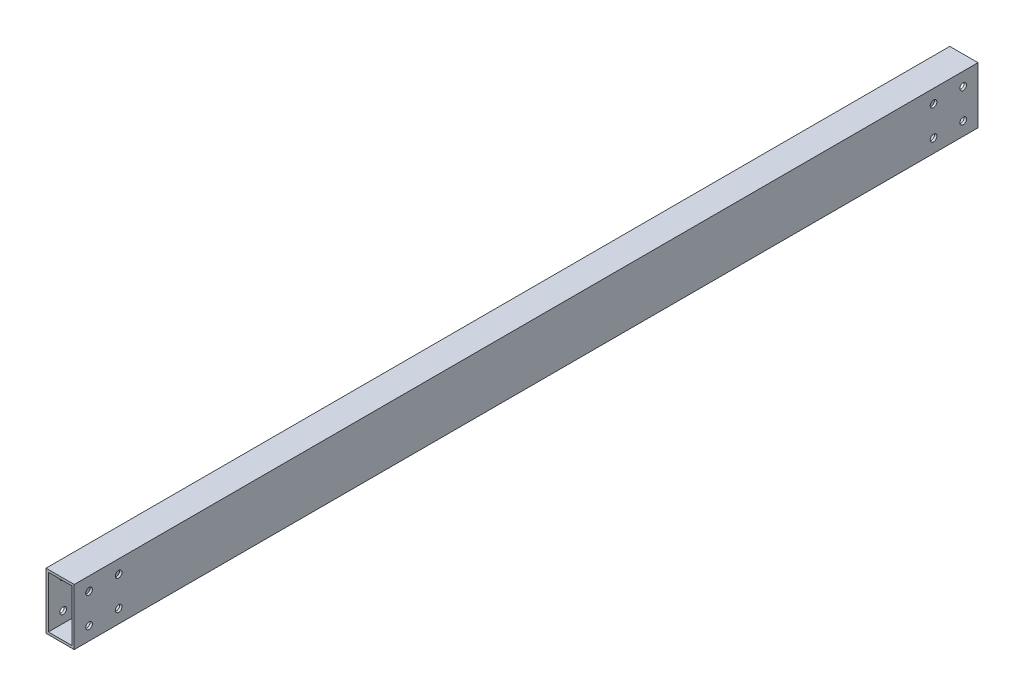
SolidWorks part; units mm, degrees
material "6061-T6 (SS)"
ref_plane "Front Plane" through (0, 0, 0) normal (0, 0, 1) x (1, 0, 0)
ref_plane "Top Plane" through (0, 0, 0) normal (0, 1, 0) x (1, 0, 0)
ref_plane "Right Plane" through (0, 0, 0) normal (1, 0, 0) x (0, 0, -1)
sketch "Sketch1" plane through (0, 0, 0) normal (0, 0, 1) x (1, 0, 0)
  line L1 (-19.05, 38.1) -> (19.05, 38.1)
  line L2 (-19.05, 38.1) -> (-19.05, -38.1)
  line L3 (-19.05, -38.1) -> (19.05, -38.1)
  line L4 (19.05, 38.1) -> (19.05, -38.1)
  line L5 (-19.05, 38.1) -> (19.05, -38.1) construction
  line L6 (-19.05, -38.1) -> (19.05, 38.1) construction
  point P0 (0, 0)
  dimension "D1" = 38.1
  dimension "D2" = 76.2
extrude "Extrude-Thin1" add sketch "Sketch1" along normal mid plane 1220 thin thin type one direction reverse wall 3.175
hole_wizard "M8 Clearance Hole2" positions "Sketch2" profile "Sketch3" hole size "M8" standard "ANSI Metric" end condition up to next
sketch "Sketch2" plane through (19.05, 0, 0) normal (1, 0, 0) x (0, 0, -1)
  line L1 (-590, 20) -> (-550, 20)
  line L2 (-590, 20) -> (-590, -20)
  line L3 (-590, -20) -> (-550, -20)
  line L4 (-550, 20) -> (-550, -20)
  line L5 (20.955, 0) -> (-20.955, 0) construction
  line L6 (-610, -38.1) -> (-610, 38.1) construction
  point P1 (-590, 20)
  point P2 (-550, -20)
  point P89 (-590, -20)
  point P90 (-550, 20)
  point P92 (-550, 0)
  dimension "D1" = 40
  dimension "D2" = 20
sketch "Sketch3" plane through (19.05, 20, 590) normal (0, 1, 0) x (0, 0, -1)
  line L0 (0, 0) -> (0, 3.175)
  line L1 (0, 3.175) -> (4.5, 3.175)
  line L2 (4.5, 3.175) -> (4.5, 0)
  line L5 (4.5, 0) -> (0, 0)
  line L11 (0, -6.35) -> (0, 107.95) construction
  dimension "Thru Hole Dia." = 9
  dimension "Thru Hole Depth" = 3.175
hole_wizard "M8 Clearance Hole1" positions "Sketch4" profile "Sketch5" hole size "M8" standard "ANSI Metric" end condition up to next
sketch "Sketch4" plane through (-15.875, 0, 0) normal (1, 0, 0) x (0, 0, -1)
  point P0 (-590, 20)
  point P3 (-550, 20)
  point P6 (-550, -20)
  point P9 (-590, -20)
sketch "Sketch5" plane through (-15.875, 20, 590) normal (0, 1, 0) x (0, 0, -1)
  line L0 (0, 0) -> (0, 3.175)
  line L1 (0, 3.175) -> (4.5, 3.175)
  line L2 (4.5, 3.175) -> (4.5, 0)
  line L5 (4.5, 0) -> (0, 0)
  line L11 (0, -6.35) -> (0, 107.95) construction
  dimension "Thru Hole Dia." = 9
  dimension "Thru Hole Depth" = 3.175
mirror "Mirror1" about plane through (0, 0, 0) normal (0, 0, 1) of "M8 Clearance Hole1", "M8 Clearance Hole2"
